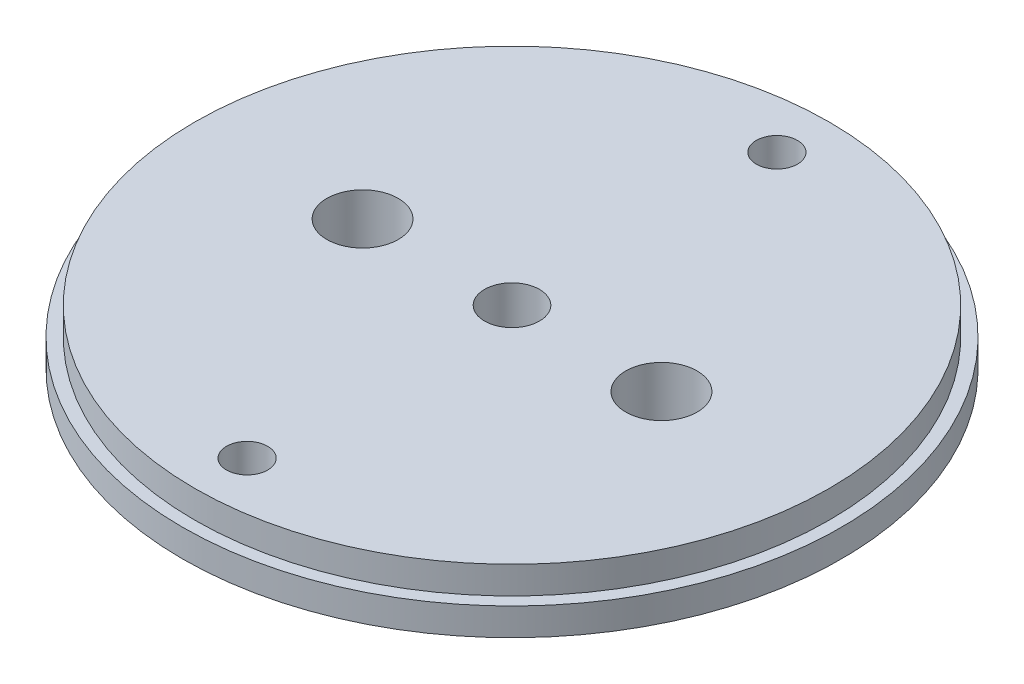
SolidWorks part; units mm, degrees
ref_plane "Front Plane" through (0, 0, 0) normal (0, 0, 1) x (1, 0, 0)
ref_plane "Top Plane" through (0, 0, 0) normal (0, 1, 0) x (1, 0, 0)
ref_plane "Right Plane" through (0, 0, 0) normal (1, 0, 0) x (0, 0, -1)
sketch "Sketch1" plane through (0, 0, 0) normal (0, 1, 0) x (1, 0, 0)
  circle A0 centre (0, 0) radius 73.3425
  circle A1 centre (0, 0) radius 76.1746
  dimension "D1" = 146.685
  dimension "D2" = 152.3492
extrude "Boss-Extrude1" add sketch "Sketch1" along normal blind 6.35 contours A0 | A1 A0 region at (0, 0, 0) region at (-74.0201, 0, 0)
extrude "Boss-Extrude2" add sketch "Sketch1<3>" along normal blind 12.7 contours A0 region at (0, 0, 0)
sketch "Sketch1<3>" plane through (0, 0, 0) normal (0, 1, 0) x (1, 0, 0) same geometry as "Sketch1"
sketch "Sketch3" plane through (0, 0, 0) normal (0, -1, 0) x (1, 0, 0)
  line L0 (34.5453, 0) -> (-34.5453, 0) construction
  line L1 (0, -61.2273) -> (0, 61.2273) construction
  circle A0 centre (0, 0) radius 6.35
  circle A1 centre (-34.5453, 0) radius 8.25
  circle A2 centre (34.5453, 0) radius 8.25
  circle A3 centre (0, 61.2273) radius 4.7625
  circle A4 centre (0, -61.2273) radius 4.7625
  point P6 (0, 0)
  point P10 (0, 61.2273)
  point P11 (28.8908, 0)
  point P14 (0, 0)
  point P15 (-34.5453, 0)
  dimension "D1" = 12.7
  dimension "D2" = 16.5001
  dimension "D3" = 9.525
extrude "Cut-Extrude1" cut sketch "Sketch3" against normal through all
sketch "Sketch5" plane through (0, 12.7, 0) normal (0, 1, 0) x (1, 0, 0)
  line L1 (7.8498, 65.9587) -> (-0.1726, 70.3911)
  line L2 (-0.1726, 70.3911) -> (-8.0224, 65.6597)
  line L3 (-8.0224, 65.6597) -> (-7.8498, 56.4959)
  line L4 (-7.8498, 56.4959) -> (0.1726, 52.0635)
  line L5 (0.1726, 52.0635) -> (8.0224, 56.7949)
  line L6 (8.0224, 56.7949) -> (7.8498, 65.9587)
  line L7 (8.6495, -58.1955) -> (1.6991, -52.2207)
  line L8 (1.6991, -52.2207) -> (-6.9503, -55.2525)
  line L9 (-6.9503, -55.2525) -> (-8.6495, -64.2591)
  line L10 (-8.6495, -64.2591) -> (-1.6991, -70.2338)
  line L11 (-1.6991, -70.2338) -> (6.9503, -67.2021)
  line L12 (6.9503, -67.2021) -> (8.6495, -58.1955)
  circle A0 centre (0, 61.2273) radius 7.9375 construction
  circle A1 centre (0, -61.2273) radius 7.9375 construction
  dimension "D1" = 15.875
